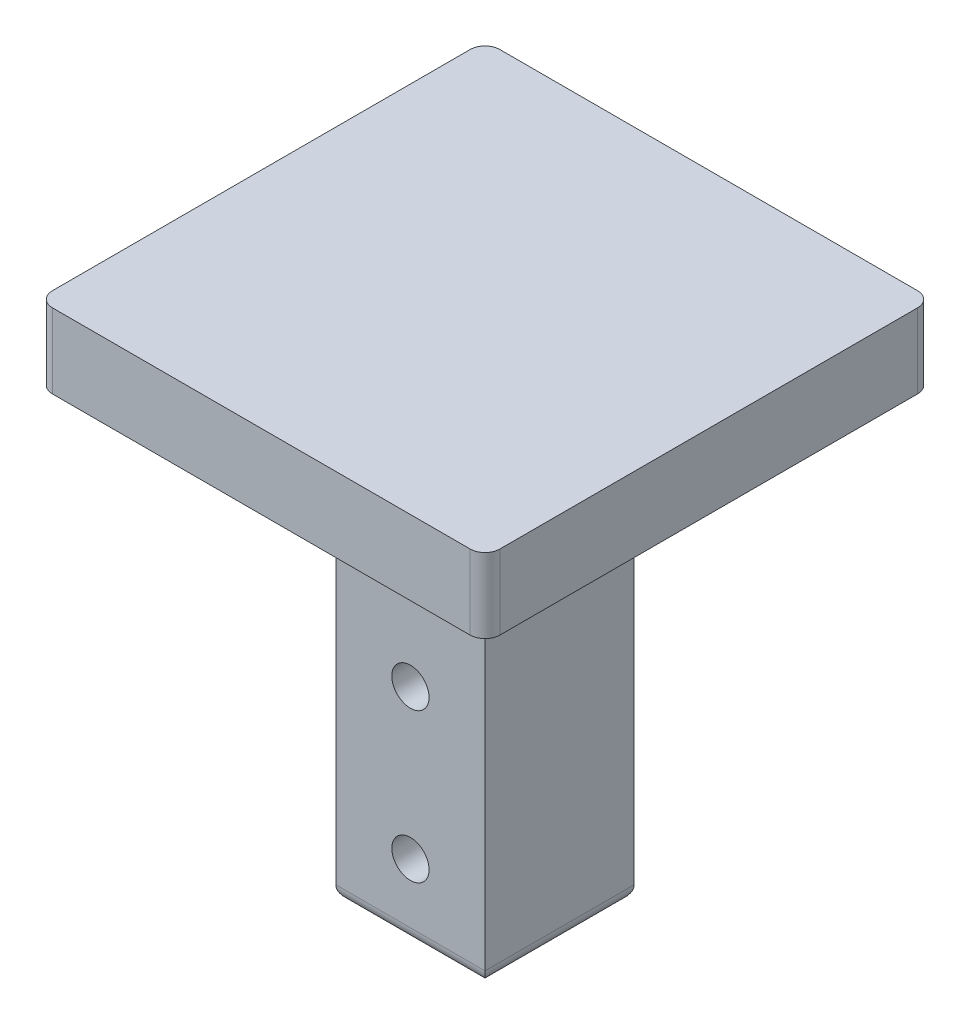
SolidWorks part; units mm, degrees
ref_plane "Front Plane" through (0, 0, 0) normal (0, 0, 1) x (1, 0, 0)
ref_plane "Top Plane" through (0, 0, 0) normal (0, 1, 0) x (1, 0, 0)
ref_plane "Right Plane" through (0, 0, 0) normal (1, 0, 0) x (0, 0, -1)
sketch "Sketch1" plane through (0, 0, 0) normal (0, 1, 0) x (1, 0, 0)
  line L1 (-10, 10) -> (10, 10)
  line L2 (-10, 10) -> (-10, -10)
  line L3 (-10, -10) -> (10, -10)
  line L4 (10, 10) -> (10, -10)
  line L5 (-10, 10) -> (10, -10) construction
  line L6 (-10, -10) -> (10, 10) construction
  point P0 (0, 0)
  point P6 (0, 0)
  point P7 (15.677, 7.0395)
  point P11 (-13.8585, 9.1885)
  dimension "D1" = 20
extrude "Boss-Extrude1" add sketch "Sketch1" against normal blind 60 contours L2 L3 L4 L1
sketch "Sketch2" plane through (0, 0, 0) normal (0, 1, 0) x (1, 0, 0)
  line L1 (-30, 30) -> (30, 30)
  line L2 (-30, 30) -> (-30, -30)
  line L3 (-30, -30) -> (30, -30)
  line L4 (30, 30) -> (30, -30)
  point P4 (30.2092, 30.5795)
  dimension "D1" = 60
  dimension "D2" = 30
  dimension "D3" = 30
extrude "Boss-Extrude2" add sketch "Sketch2" along normal blind 10
fillet "Fillet1" radius 2 8 edges at (0, -60, -10) (-10, -60, 0) (0, -60, 10) (10, -60, 0) (30, 5, 30) (30, 5, -30) (-30, 5, -30) (-30, 5, 30)
sketch "Sketch3" plane through (0, 0, 10) normal (0, 0, 1) x (1, 0, 0)
  line L0 (-10, 0) -> (10, 0) construction
  circle A0 centre (0, -30) radius 2.5
  circle A1 centre (0, -50) radius 2.5
  dimension "D3" = 5
  dimension "D1" = 20
  dimension "D2" = 30
extrude "Cut-Extrude1" cut sketch "Sketch3" against normal through all
